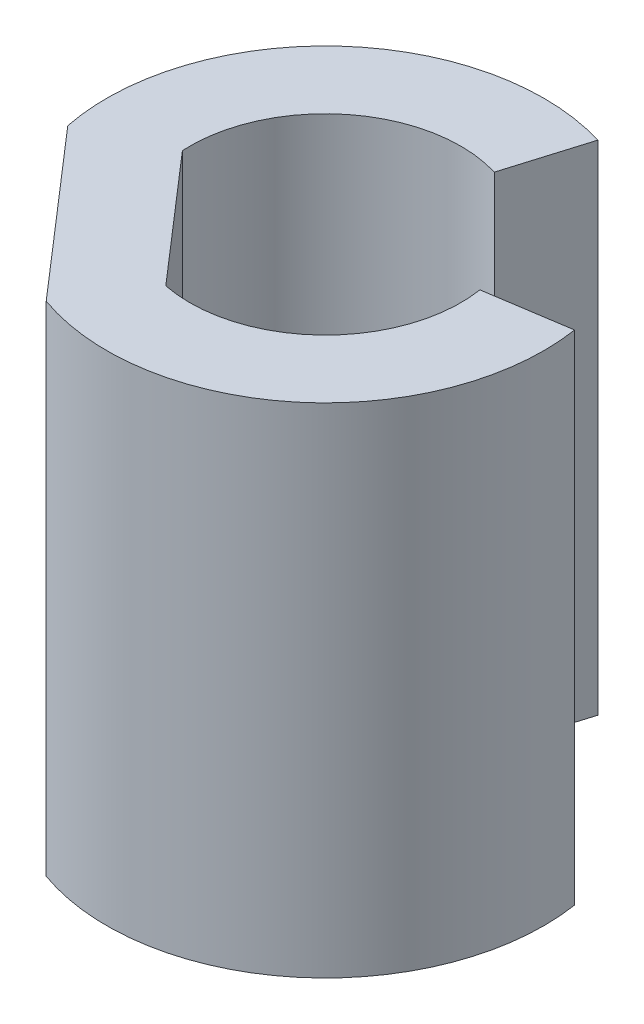
SolidWorks part; units mm, degrees
ref_plane "Front Plane" through (0, 0, 0) normal (0, 0, 1) x (1, 0, 0)
ref_plane "Top Plane" through (0, 0, 0) normal (0, 1, 0) x (1, 0, 0)
ref_plane "Right Plane" through (0, 0, 0) normal (1, 0, 0) x (0, 0, -1)
sketch "Sketch1" plane through (0, 0, 0) normal (0, 1, 0) x (1, 0, 0)
  line L6 (-0.4803, -2.4025) -> (-2.4462, -0.1363)
  line L7 (-1.3209, -3.7226) -> (-3.8718, -0.782)
  line L8 (1.1424, 3.7812) -> (0.7086, 2.3453)
  line L9 (2.4216, 0.3722) -> (3.9041, 0.6001)
  arc A7 (-0.4803, -2.4025) -> (2.4216, 0.3722) centre (0, 0) ccw
  arc A8 (-2.4462, -0.1363) -> (0.7086, 2.3453) centre (0, 0) cw
  arc A9 (-1.3209, -3.7226) -> (3.9041, 0.6001) centre (0, 0) ccw
  arc A10 (-3.8718, -0.782) -> (1.1424, 3.7812) centre (0, 0) cw
  dimension "D1" = 2.45
  dimension "D3" = 3
  dimension "D2" = 2.45
  dimension "D4" = 1.5
extrude "Boss-Extrude1" add sketch "Sketch1" along normal blind 9
